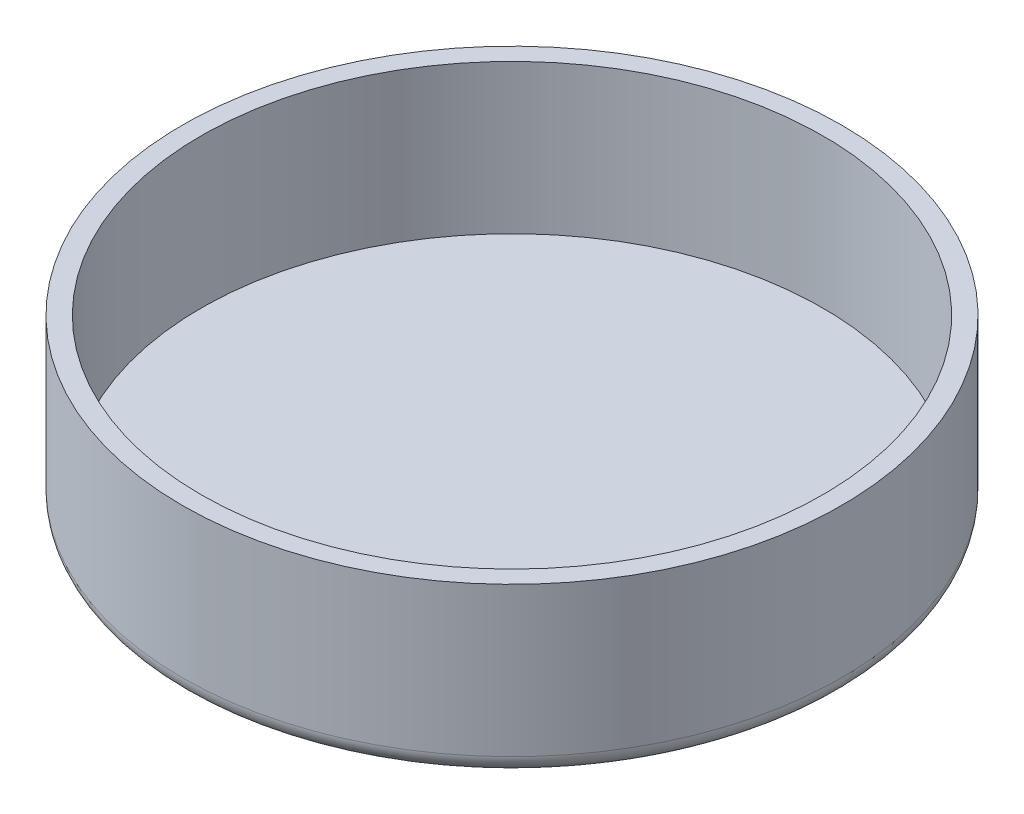
SolidWorks part; units mm, degrees
ref_plane "Front Plane" through (0, 0, 0) normal (0, 0, 1) x (1, 0, 0)
ref_plane "Top Plane" through (0, 0, 0) normal (0, 1, 0) x (1, 0, 0)
ref_plane "Right Plane" through (0, 0, 0) normal (1, 0, 0) x (0, 0, -1)
sketch "Sketch1" plane through (0, 0, 0) normal (0, 1, 0) x (1, 0, 0)
  circle A0 centre (0, 0) radius 50
  circle A1 centre (0, 0) radius 53
extrude "Boss-Extrude1" add sketch "Sketch1" along normal blind 27
extrude "Boss-Extrude2" add sketch "Sketch1<2>" along normal blind 3 contours A1
sketch "Sketch1<2>" plane through (0, 0, 0) normal (0, 1, 0) x (1, 0, 0) same geometry as "Sketch1"
fillet "Fillet1" radius 3 1 edges at (0, 0, 53)
